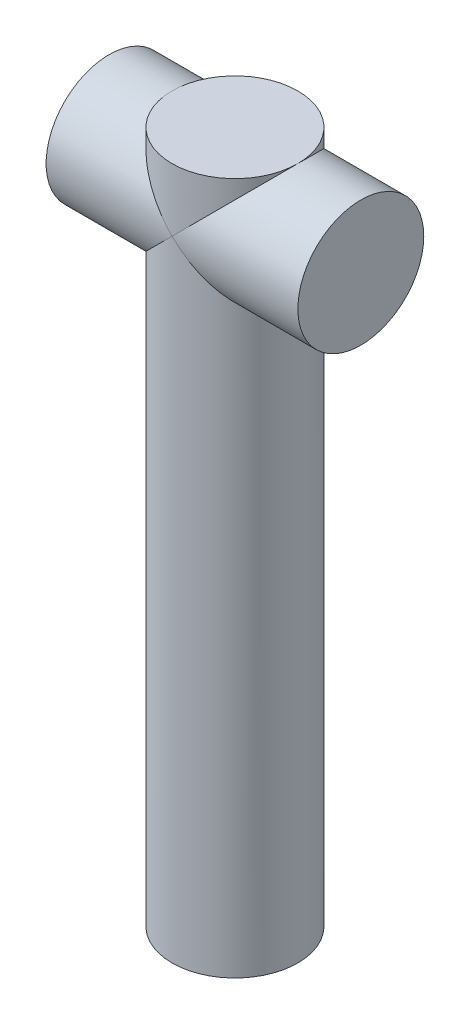
SolidWorks part; units mm, degrees
ref_plane "Plano frontal" through (0, 0, 0) normal (0, 0, 1) x (1, 0, 0)
ref_plane "Plano superior" through (0, 0, 0) normal (0, 1, 0) x (1, 0, 0)
ref_plane "Plano direito" through (0, 0, 0) normal (1, 0, 0) x (0, 0, -1)
sketch "Esboço1" plane through (0, 0, 0) normal (0, 1, 0) x (1, 0, 0)
  circle A0 centre (0, 0) radius 15
  dimension "D1" = 30
extrude "Ressalto-extrusão1" add sketch "Esboço1" against normal blind 165
sketch "Esboço3" plane through (0, 0, 0) normal (1, 0, 0) x (0, 0, -1)
  line L0 (15, -165) -> (15, 0) construction
  line L1 (15, 0) -> (-15, 0) construction
  circle A0 centre (0, -15) radius 15
  dimension "D1" = 30
extrude "Ressalto-extrusão2" add sketch "Esboço3" along normal blind 30 and the other way blind 30
